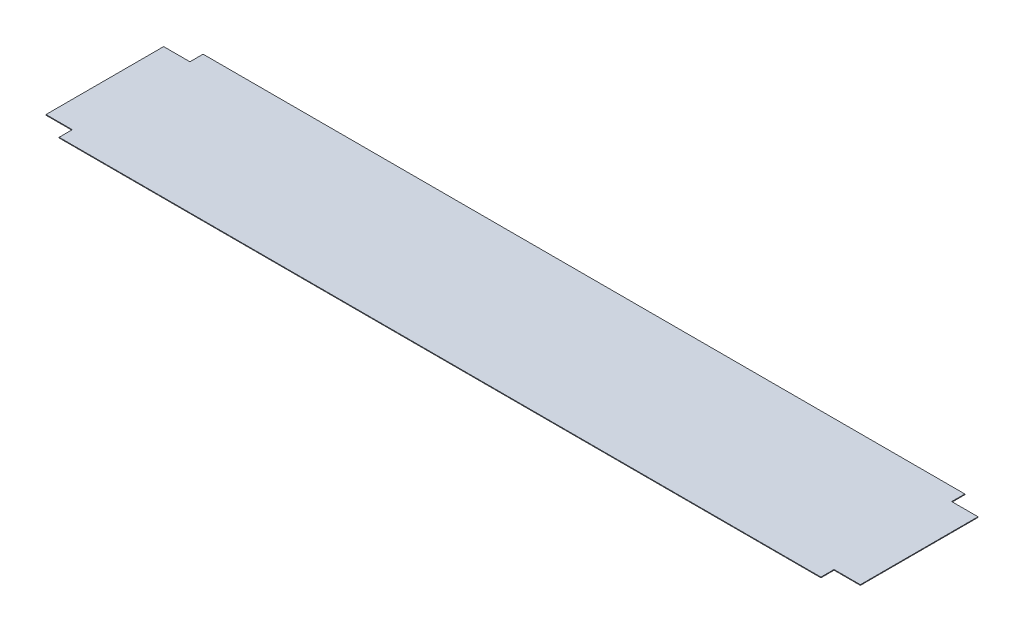
SolidWorks part; units mm, degrees
ref_plane "Front Plane" through (0, 0, 0) normal (0, 0, 1) x (1, 0, 0)
ref_plane "Top Plane" through (0, 0, 0) normal (0, 1, 0) x (1, 0, 0)
ref_plane "Right Plane" through (0, 0, 0) normal (1, 0, 0) x (0, 0, -1)
sketch "Sketch1" plane through (0, 0, 0) normal (0, 1, 0) x (1, 0, 0)
  line L0 (579.5, 109.5) -> (579.5, 89.5)
  line L1 (-579.5, -109.5) -> (579.5, -109.5)
  line L2 (-619.5, -89.5) -> (-619.5, 89.5)
  line L3 (-579.5, 109.5) -> (579.5, 109.5)
  line L4 (619.5, -89.5) -> (619.5, 89.5)
  line L5 (579.5, 89.5) -> (619.5, 89.5)
  line L6 (0, 0) -> (0, 109.5) construction
  line L7 (-579.5, 89.5) -> (-619.5, 89.5)
  line L8 (-579.5, 109.5) -> (-579.5, 89.5)
  line L9 (621, 0) -> (551.7539, 0) construction
  line L10 (-579.5, -89.5) -> (-619.5, -89.5)
  line L11 (-579.5, -109.5) -> (-579.5, -89.5)
  line L12 (579.5, -109.5) -> (579.5, -89.5)
  line L13 (579.5, -89.5) -> (619.5, -89.5)
  point P0 (-579.5, 99.5)
  dimension "D1" = 40
  dimension "D2" = 1159
  dimension "D3" = 179
  dimension "D4" = 20
base flange "Base-Flange1" sketch "Sketch1" thickness 1 reverse thickness direction no parameters "D1"=1
sketch "Bend-Lines1" [suppressed] plane through (0, 0, 0) normal (0, 1, 0) x (1, 0, 0)
sketch "Bounding-Box1" [suppressed] plane through (0, 0, 0) normal (0, 1, 0) x (1, 0, 0)
sheet metal parameters "Sheet-Metal1" thickness 1 parameters "D1"=1
flat pattern "Flat-Pattern1" [suppressed]
sketch "Bend-Lines2" plane through (0, 0, 0) normal (0, 1, 0) x (1, 0, 0)
sketch3d "Bounding-Box2" [suppressed]
  line L0 (619.5, 109.5, 0) -> (-619.5, 109.5, 0) construction
  line L1 (619.5, -109.5, 0) -> (-619.5, -109.5, 0) construction
  line L2 (619.5, 109.5, 0) -> (619.5, -109.5, 0) construction
  line L3 (-619.5, 109.5, 0) -> (-619.5, -109.5, 0) construction
